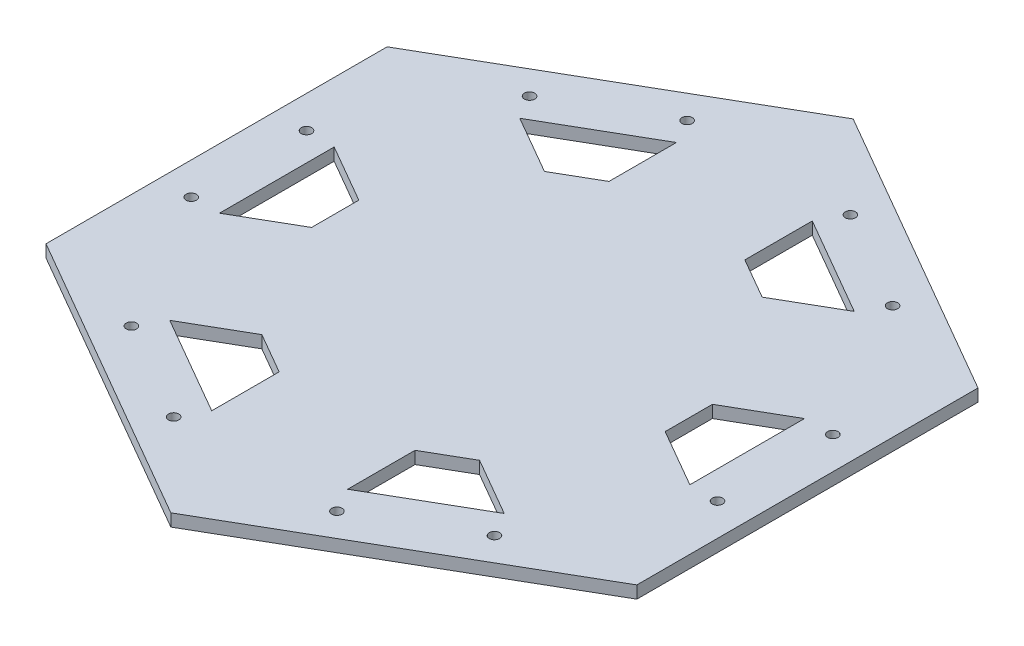
SolidWorks part; units mm, degrees
ref_plane "Front Plane" through (0, 0, 0) normal (0, 0, 1) x (1, 0, 0)
ref_plane "Top Plane" through (0, 0, 0) normal (0, 1, 0) x (1, 0, 0)
ref_plane "Right Plane" through (0, 0, 0) normal (1, 0, 0) x (0, 0, -1)
sketch "Sketch2" plane through (0, 0, 0) normal (0, 1, 0) x (1, 0, 0)
  line L1 (0, -117.3176) -> (101.6, -58.6588)
  line L2 (101.6, -58.6588) -> (101.6, 58.6588)
  line L3 (101.6, 58.6588) -> (0, 117.3176)
  line L4 (0, 117.3176) -> (-101.6, 58.6588)
  line L5 (-101.6, 58.6588) -> (-101.6, -58.6588)
  line L6 (-101.6, -58.6588) -> (0, -117.3176)
  circle A0 centre (0, 0) radius 101.6 construction
  dimension "D1" = 203.2
extrude "Boss-Extrude1" add sketch "Sketch2" along normal blind 4.25
sketch "Sketch3" plane through (0, 4.25, 0) normal (0, 1, 0) x (1, 0, 0)
  line L0 (-101.6, 0) -> (101.6, 0)
  line L1 (-101.6, 58.6588) -> (-101.6, -58.6588) construction
  line L2 (101.6, -58.6588) -> (101.6, 58.6588) construction
  line L3 (-50.8, 87.9882) -> (50.8, -87.9882)
  line L4 (0, 117.3176) -> (-101.6, 58.6588) construction
  line L5 (0, -117.3176) -> (101.6, -58.6588) construction
  line L6 (50.8, 87.9882) -> (-50.8, -87.9882)
  line L7 (101.6, 58.6588) -> (0, 117.3176) construction
  line L8 (-101.6, -58.6588) -> (0, -117.3176) construction
  line L10 (-23.365, -79.9024) -> (-23.365, -56.716)
  line L13 (-101.6, -58.6588) -> (0, 0)
  line L14 (-57.515, -60.1859) -> (-37.435, -48.5927)
  line L15 (-57.515, -60.1859) -> (-23.365, -79.9024)
  line L16 (-23.365, -56.716) -> (-37.435, -48.5927)
  line L17 (-80.88, 19.7165) -> (-60.8, 8.1234)
  line L18 (-80.88, -19.7165) -> (-80.88, 19.7165)
  line L19 (-80.88, -19.7165) -> (-60.8, -8.1234)
  line L20 (-60.8, 8.1234) -> (-60.8, -8.1234)
  line L21 (0, 0) -> (0, -117.3176)
  line L22 (-101.6, 58.6588) -> (101.6, -58.6588)
  line L23 (23.365, -79.9024) -> (23.365, -56.716)
  line L24 (57.515, -60.1859) -> (23.365, -79.9024)
  line L25 (57.515, -60.1859) -> (37.435, -48.5927)
  line L26 (23.365, -56.716) -> (37.435, -48.5927)
  line L27 (80.88, -19.7165) -> (60.8, -8.1234)
  line L28 (60.8, 8.1234) -> (60.8, -8.1234)
  line L29 (80.88, -19.7165) -> (80.88, 19.7165)
  line L30 (80.88, 19.7165) -> (60.8, 8.1234)
  line L31 (57.515, 60.1859) -> (37.435, 48.5927)
  line L32 (23.365, 79.9024) -> (57.515, 60.1859)
  line L33 (37.435, 48.5927) -> (23.365, 56.716)
  line L34 (23.365, 79.9024) -> (23.365, 56.716)
  line L35 (-23.365, 79.9024) -> (-23.365, 56.716)
  line L36 (-23.365, 79.9024) -> (-57.515, 60.1859)
  line L37 (-57.515, 60.1859) -> (-37.435, 48.5927)
  line L38 (-37.435, 48.5927) -> (-23.365, 56.716)
extrude "Cut-Extrude1" cut sketch "Sketch3" against normal blind 4.25 contours L6 L16 L14 L15 | L10 L16 L6 L15 | L26 L23 L24 L3 | L26 L3 L24 L25 | L27 L29 L0 L28 | L29 L30 L28 L0 | L33 L31 L32 L6 | L32 L34 L33 L6 | L37 L38 L3 L36 | L3 L38 L35 L36 | L17 L20 L19 L18 region at (-42.4927, 4.25, -58.875) region at (-29.7409, 4.25, -66.2373) region at (29.7409, 4.25, -66.2373) region at (42.4927, 4.25, -58.875) region at (72.2336, 4.25, -7.3623) region at (72.2336, 4.25, 7.3623) region at (42.4927, 4.25, 58.875) region at (29.7409, 4.25, 66.2373) region at (-29.7409, 4.25, 66.2373) region at (-42.4927, 4.25, 58.875)
sketch "Sketch4" plane through (0, 4.25, 0) normal (0, 1, 0) x (1, 0, 0)
  line L0 (0, 0) -> (-101.6, 0) construction
  line L1 (-101.6, 58.6588) -> (-101.6, -58.6588) construction
  line L2 (-90.5, 0) -> (-90.5, 19.83) construction
  line L4 (-101.6, -58.6588) -> (101.6, 58.6588) construction
  line L5 (0, -117.3176) -> (0, 117.3176) construction
  line L6 (0, 0) -> (-101.6, 58.6588) construction
  point P8 (-90.5, -19.83)
  point P16 (0, 0)
  point P17 (-62.4233, 68.4603)
  point P20 (-28.0767, 88.2903)
  point P21 (0, 0)
  point P22 (-62.4233, -68.4603)
  point P23 (-28.0767, -88.2903)
  point P24 (0, 0)
  point P25 (28.0767, -88.2903)
  point P26 (62.4233, -68.4603)
  point P27 (90.5, -19.83)
  point P28 (90.5, 19.83)
  point P29 (62.4233, 68.4603)
  point P30 (28.0767, 88.2903)
  dimension "D1" = 11.1
hole_wizard "#37 (0.14015748) Diameter Hole1" positions "Sketch5" profile "Sketch6" hole size "#37" standard "ANSI Inch" end condition through all
sketch "Sketch5" plane through (0, 4.25, 0) normal (0, 1, 0) x (1, 0, 0)
  point P0 (62.4233, 68.4603)
  point P3 (90.5, 19.83)
  point P6 (90.5, -19.83)
  point P9 (62.4233, -68.4603)
  point P12 (28.0767, -88.2903)
  point P15 (-28.0767, -88.2903)
  point P18 (-62.4233, -68.4603)
  point P21 (-90.5, -19.83)
  point P24 (-90.5, 19.83)
  point P27 (-62.4233, 68.4603)
  point P30 (-28.0767, 88.2903)
  point P33 (28.0767, 88.2903)
sketch "Sketch6" plane through (62.4233, 4.25, -68.4603) normal (1, 0, 0) x (0, 0, 1)
  line L0 (0, 0) -> (0, 4.25)
  line L1 (0, 4.25) -> (1.78, 4.25)
  line L2 (1.78, 4.25) -> (1.78, 0)
  line L5 (1.78, 0) -> (0, 0)
  line L11 (0, -6.35) -> (0, 107.95) construction
  dimension "Thru Hole Dia." = 3.56
  dimension "Thru Hole Depth" = 4.25
